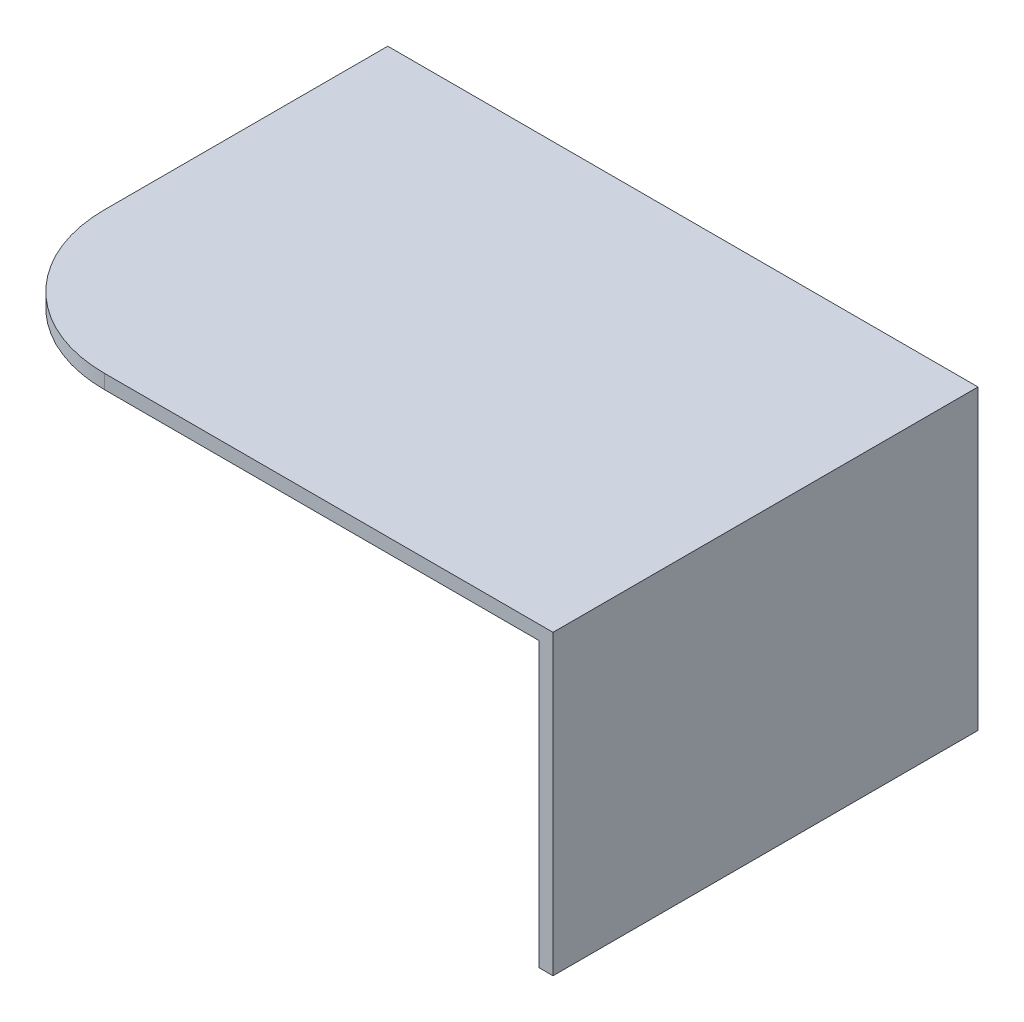
SolidWorks part; units mm, degrees
ref_plane "Front Plane" through (0, 0, 0) normal (0, 0, 1) x (1, 0, 0)
ref_plane "Top Plane" through (0, 0, 0) normal (0, 1, 0) x (1, 0, 0)
ref_plane "Right Plane" through (0, 0, 0) normal (1, 0, 0) x (0, 0, -1)
sketch "Sketch2" plane through (0, 0, 0) normal (0, 0, 1) x (1, 0, 0)
  line L0 (0, 4.05) -> (2.5, 4.05)
  line L1 (0, -4.05) -> (10.5, -4.05)
  line L2 (2.5, 4.05) -> (2.5, 30.95)
  line L3 (2.5, 30.95) -> (-49.5, 30.95)
  line L4 (-49.5, 30.95) -> (-49.5, 33.95)
  line L5 (-49.5, 33.95) -> (10.5, 33.95)
  line L6 (10.5, 33.95) -> (10.5, -4.05)
  line L7 (2.5, 30.95) -> (10.5, 30.95)
  line L8 (10.5, 33.95) -> (75.5, 33.95)
  line L9 (75.5, 33.95) -> (75.5, -29.05)
  line L10 (75.5, -29.05) -> (10.5, -29.05)
  line L11 (10.5, -29.05) -> (10.5, -4.05)
  line L12 (10.5, 30.95) -> (72.5, 30.95)
  line L13 (30.5, 33.95) -> (30.5, 30.95)
  line L14 (72.5, 30.95) -> (72.5, -29.05)
  point P4 (0, 0)
  point P11 (72.5, 30.95)
  point P17 (71.5038, 30.95)
  point P20 (75.5, 33.95)
  point P22 (75.5, 33.1647)
  line B0 (0, -7.95) -> (-2.04, -7.95)
  line B1 (-6.1524, -4.048) -> (-6.1524, 4.048)
  line B2 (-2.04, 7.95) -> (0, 7.95)
  line B3 (0, 7.95) -> (0, -7.95)
  line B4 (-2.04, -7.95) -> (-6.1524, -4.048)
  line B5 (-6.1524, 4.048) -> (-2.04, 7.95)
  line B6 (0, -4.05) -> (0, 4.05) construction
  dimension "D1" = 10.5
  dimension "D2" = 8
  dimension "D3" = 3
  dimension "D4" = 60
  dimension "D5" = 35
  dimension "D6" = 65
  dimension "D7" = 60
  dimension "D8" = 20
  dimension "D9" = 3
sketch_block_instance "Extrusion Profile-1"
sketch_block "Block1" parameters "D1"=8.44, "D2"=2.6, "D3"=6, "D4"=16.7, "D6"=5.6686, "D7"=2.0404, "D8"=8.0963, "D9"=15.9, "D5"=2.4157
extrude "Boss-Extrude1" add sketch "Sketch2" along normal blind 6 contours L0 B3 L1 L6 L7 L2 | B2 B5 B1 B4 B0 B3 region at (-2.7416, 0, 0) region at (6.1459, 12.5429, 0)
extrude "Boss-Extrude2" add sketch "Sketch2<3>" along normal blind 90 contours L3 L7 L6 L5 L4 | L13 L8 L6 | L12 L14 L10 L9 L8 L13 region at (-19.5, 32.45, 0) region at (20.5, 32.45, 0) region at (31.2742, 32.45, 0)
sketch "Sketch2<3>" plane through (0, 0, 0) normal (0, 0, 1) x (1, 0, 0) same geometry as "Sketch2"
extrude "Boss-Extrude3" add sketch "Sketch2<4>" along normal blind 3 contours L6 L11 L10 L9 | L8 L13 L9 region at (41.5, 0.95, 0) region at (31.2742, 32.45, 0)
sketch "Sketch2<4>" plane through (0, 0, 0) normal (0, 0, 1) x (1, 0, 0) same geometry as "Sketch2"
fillet "Fillet1" radius 3 1 edges at (10.5, 13.45, 3)
fillet "Fillet2" radius 3 1 edges at (10.5, 13.45, 6)
fillet "Fillet3" radius 30 1 edges at (-49.5, 32.45, 90)
sketch "Sketch3" plane through (0, 0, 0) normal (0, 0, -1) x (-1, 0, 0)
  line L0 (-2.5, 4.05) -> (-2.5, -4.05)
  line L1 (0, -4.05) -> (-10.5, -4.05) construction
  line L18 (49.5, 33.95) -> (-75.5, 33.95)
  line L19 (-75.5, 33.95) -> (-75.5, -29.05)
  line L20 (-75.5, -29.05) -> (-10.5, -29.05)
  line L21 (-10.5, -29.05) -> (-10.5, -4.05)
  line L22 (-10.5, -4.05) -> (0, -4.05)
  line L23 (0, -4.05) -> (0, -7.95)
  line L24 (0, -7.95) -> (2.04, -7.95)
  line L25 (2.04, -7.95) -> (6.1524, -4.048)
  line L26 (6.1524, -4.048) -> (6.1524, 4.048)
  line L27 (6.1524, 4.048) -> (2.04, 7.95)
  line L28 (2.04, 7.95) -> (0, 7.95)
  line L29 (0, 7.95) -> (0, 4.05)
  line L30 (0, 4.05) -> (-2.5, 4.05)
  line L31 (-2.5, 4.05) -> (-2.5, 30.95)
  line L32 (-2.5, 30.95) -> (49.5, 30.95)
  line L33 (49.5, 30.95) -> (49.5, 33.95)
  line L34 (49.5, 33.95) -> (-75.5, 33.95)
  line L35 (-75.5, 33.95) -> (-75.5, -29.05)
  line L36 (-75.5, -29.05) -> (-10.5, -29.05)
  line L37 (-10.5, -29.05) -> (-10.5, -4.05)
  line L38 (-10.5, -4.05) -> (-2.5, -4.05)
  line L47 (-2.5, 4.05) -> (-2.5, 30.95)
  line L48 (-2.5, 30.95) -> (49.5, 30.95)
  line L49 (49.5, 30.95) -> (49.5, 33.95)
  dimension "D1" = 0
sketch "Sketch4" plane through (0, 0, 0) normal (0, 0, -1) x (-1, 0, 0)
  line L0 (6.1524, 1) -> (6.1524, -1)
  line L1 (6.1524, -4.048) -> (6.1524, 4.048) construction
  line L2 (6.1524, -1) -> (2.1524, -1)
  line L3 (2.1524, -1) -> (2.1524, 1)
  line L4 (2.1524, 1) -> (6.1524, 1)
  point P5 (6.1524, 0)
  dimension "D1" = 2
  dimension "D2" = 4
extrude "Cut-Extrude1" cut sketch "Sketch4" against normal through all
